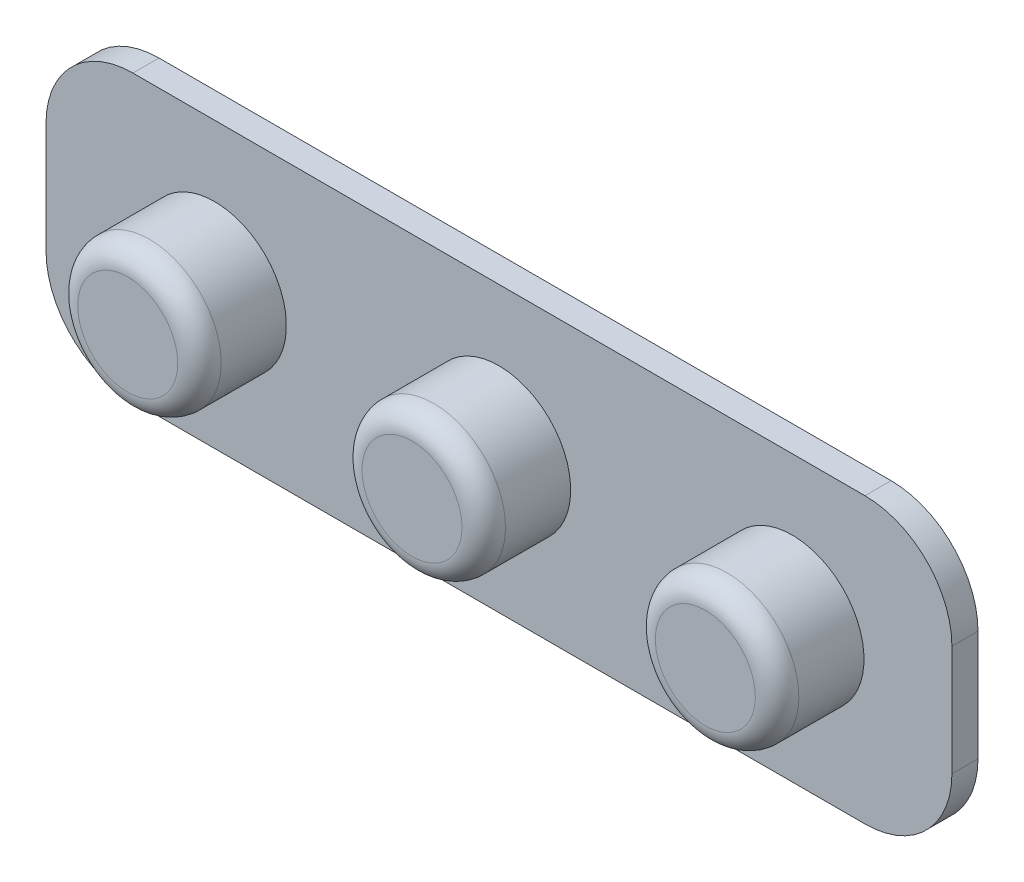
SolidWorks part; units mm, degrees
ref_plane "Front Plane" through (0, 0, 0) normal (0, 0, 1) x (1, 0, 0)
ref_plane "Top Plane" through (0, 0, 0) normal (0, 1, 0) x (1, 0, 0)
ref_plane "Right Plane" through (0, 0, 0) normal (1, 0, 0) x (0, 0, -1)
sketch "Sketch1" plane through (0, 0, 0) normal (0, 0, 1) x (1, 0, 0)
  line L0 (-33.093, -3.6337) -> (71.1175, -3.6337)
  line L1 (-33.093, 12.7181) -> (71.1175, 12.7181)
  line L2 (-33.093, 12.7181) -> (-33.093, -19.9856)
  line L3 (-33.093, -19.9856) -> (71.1175, -19.9856)
  line L4 (71.1175, 12.7181) -> (71.1175, -19.9856)
  circle A0 centre (19.0123, -3.6337) radius 8.25
  circle A1 centre (-13.6914, -3.6337) radius 8.25
  circle A2 centre (52.7542, -3.6337) radius 8.25
  dimension "D1" = 16.5
  dimension "D2" = 16.5
  dimension "D3" = 16.5
extrude "Boss-Extrude1" add sketch "Sketch1" along normal blind 3 contours A2 L0 L4 L1 L2 A1 A0 | A2 L0 A0 A1 L2 L3 L4 | L0 A1 | L0 A1 | L0 A0 | L0 A0 | L0 A2 | L0 A2 region at (18.932, 5.626, 0) region at (52.7542, -7.1352, 0) region at (52.7542, -0.1323, 0) region at (18.932, -12.8935, 0) region at (19.0123, -7.1352, 0) region at (19.0123, -0.1323, 0) region at (-13.6914, -7.1352, 0) region at (-13.6914, -0.1323, 0)
extrude "Boss-Extrude2" add sketch "Sketch1<3>" along normal blind 13 contours L0 A1 | L0 A1 | L0 A0 | L0 A0 | L0 A2 | L0 A2 region at (52.7542, -7.1352, 0) region at (52.7542, -0.1323, 0) region at (19.0123, -7.1352, 0) region at (19.0123, -0.1323, 0) region at (-13.6914, -7.1352, 0) region at (-13.6914, -0.1323, 0)
sketch "Sketch1<3>" plane through (0, 0, 0) normal (0, 0, 1) x (1, 0, 0) same geometry as "Sketch1"
fillet "Fillet1" radius 10 4 edges at (71.1175, 12.7181, 1.5) (71.1175, -19.9856, 1.5) (-33.093, -19.9856, 1.5) (-33.093, 12.7181, 1.5)
fillet "Fillet2" radius 2.5 3 edges at (61.0042, -3.6337, 13) (27.2623, -3.6337, 13) (-5.4414, -3.6337, 13)
